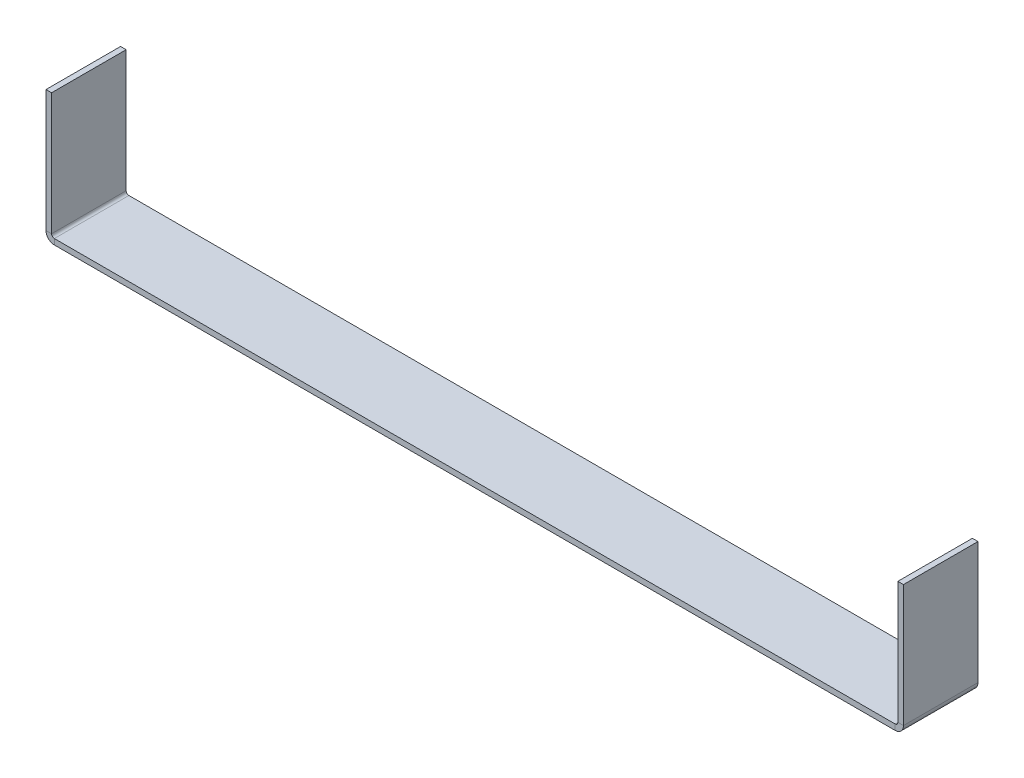
SolidWorks part; units mm, degrees
note: The reader was unsure of these and kept them because the rebuilt part matched: flange length of "Ребро-кромка1", "Ребро-кромка2".
ref_plane "Спереди" through (0, 0, 0) normal (0, 0, 1) x (1, 0, 0)
ref_plane "Сверху" through (0, 0, 0) normal (0, 1, 0) x (1, 0, 0)
ref_plane "Справа" through (0, 0, 0) normal (1, 0, 0) x (0, 0, -1)
sketch "Эскиз1" plane through (0, 0, 0) normal (0, 1, 0) x (1, 0, 0)
  line L1 (0, 0) -> (230, 0)
  line L2 (0, 0) -> (0, 20)
  line L3 (0, 20) -> (230, 20)
  line L4 (230, 0) -> (230, 20)
base flange "Базовая кромка1" sketch "Эскиз1" thickness 1.5 reverse thickness direction no parameters "D1"=0.7366
edge flange "Ребро-кромка1" sketch "Эскиз8" flange angle 90 flange length 35 flange position material inside bend radius 0.7366 thickness 1.5 relief rectangular parameters "D6"=10
sketch "Эскиз8" plane through (0, 0, 0) normal (-1, 0, 0) x (0, 0, 1)
  line L0 (-20, 0) -> (0, 0) construction
  line L1 (-20, 0) -> (0, 0)
  line L2 (-20, 0) -> (-20, 33.5)
  line L3 (-20, 33.5) -> (0, 33.5)
  line L4 (0, 33.5) -> (0, 0)
bend "EdgeBend1" bend radius 0.7366 bend angle 90 parameters "D5"=1
edge flange "Ребро-кромка2" sketch "Эскиз11" flange angle 90 flange length 35 flange position material inside bend radius 0.7366 thickness 1.5 relief rectangular parameters "D6"=10
sketch "Эскиз11" plane through (230, 0, 0) normal (1, 0, 0) x (0, 0, -1)
  line L2 (0, 0) -> (0, 33.5)
  line L3 (0, 33.5) -> (20, 33.5)
  line L4 (20, 33.5) -> (20, 0)
  line L7 (0, 0) -> (20, 0) construction
  line L8 (0, 0) -> (20, 0)
bend "EdgeBend2" bend radius 0.7366 bend angle 90 parameters "D5"=2
sketch "Сгиб-Линии1" [suppressed] plane through (0, 0, 0) normal (0, 1, 0) x (1, 0, 0)
sketch "Граничная рамка1" [suppressed] plane through (0, 0, 0) normal (0, 1, 0) x (1, 0, 0)
sheet metal parameters "Листовой металл1" thickness 1.5 parameters "D1"=0.7366
flat pattern "Развертка1" [suppressed]
sketch "Сгиб-Линии2" plane through (0, 0, 0) normal (0, 1, 0) x (1, 0, 0)
sketch3d "Граничная рамка2" [suppressed]
  line L0 (-200, 20, 0) -> (0, 20, 0) construction
  line L1 (-200, 0, 0) -> (0, 0, 0) construction
  line L2 (-200, 20, 0) -> (-200, 0, 0) construction
  line L3 (0, 20, 0) -> (0, 0, 0) construction
sheet metal parameters "Листовой металл2" thickness 1.5 parameters "D1"=0.7366
flat pattern "Развертка1"
sketch "Сгиб-Линии2" plane through (0, 0, 0) normal (0, 1, 0) x (1, 0, 0)
  line L0 (1.069, 20) -> (1.069, 0) construction
  line L1 (1.069, 20) -> (1.069, 0) construction
sketch3d "Граничная рамка2" [suppressed]
  line L0 (200, 20, 0) -> (-30.5985, 20, 0) construction
  line L1 (200, 0, 0) -> (-30.5985, 0, 0) construction
  line L2 (200, 20, 0) -> (200, 0, 0) construction
  line L3 (-30.5985, 20, 0) -> (-30.5985, 0, 0) construction
bend of the flat pattern "Плоское состояние-<EdgeBend1>1"
sheet metal parameters "Листовой металл3" thickness 1.5 parameters "D1"=0.7366
flat pattern "Развертка1"
sketch "Сгиб-Линии2" plane through (0, 0, 0) normal (0, 1, 0) x (1, 0, 0)
  line L0 (1.069, 20) -> (1.069, 0) construction
  line L1 (1.069, 20) -> (1.069, 0) construction
  line L2 (228.931, 0) -> (228.931, 20) construction
  line L3 (228.931, 0) -> (228.931, 20) construction
sketch3d "Граничная рамка2" [suppressed]
  line L0 (262.8619, 20, 0) -> (-32.8619, 20, 0) construction
  line L1 (262.8619, 0, 0) -> (-32.8619, 0, 0) construction
  line L2 (262.8619, 20, 0) -> (262.8619, 0, 0) construction
  line L3 (-32.8619, 20, 0) -> (-32.8619, 0, 0) construction
bend of the flat pattern "Плоское состояние-<EdgeBend1>1"
bend of the flat pattern "Плоское состояние-<EdgeBend2>1"
